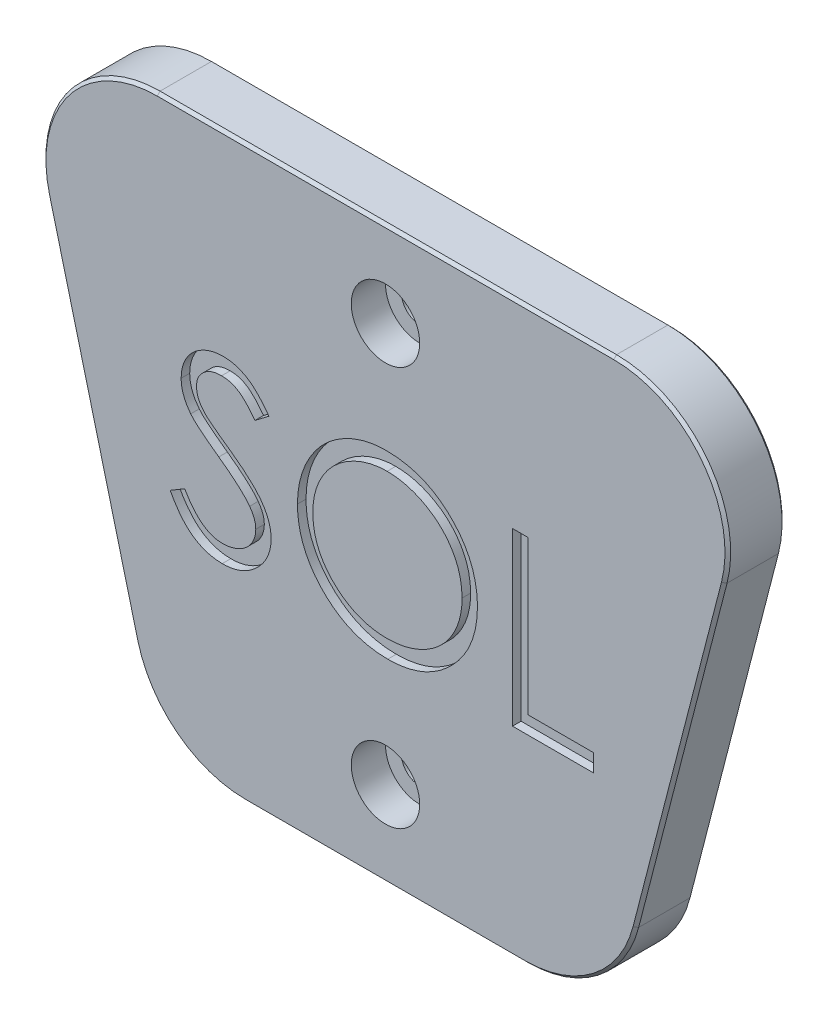
SolidWorks part; units mm, degrees
ref_plane "Front Plane" through (0, 0, 0) normal (0, 0, 1) x (1, 0, 0)
ref_plane "Top Plane" through (0, 0, 0) normal (0, 1, 0) x (1, 0, 0)
ref_plane "Right Plane" through (0, 0, 0) normal (1, 0, 0) x (0, 0, -1)
sketch "Sketch2" plane through (0, 0, 0) normal (0, 0, 1) x (1, 0, 0)
  line L0 (20, -80) -> (100, -80)
  line L6 (100, 20) -> (20, 20)
  line L8 (0.6351, -5) -> (20, -80)
  line L9 (119.3649, -5) -> (100, -80)
  line L10 (120, 23.0116) -> (120, 0)
  line L11 (0, 0) -> (0, 50.4461)
  line L12 (60, 20) -> (60, -80) construction
  arc A4 (119.3649, -5) -> (100, 20) centre (100, 0) ccw
  arc A5 (0.6351, -5) -> (20, 20) centre (20, 0) cw
  point P2 (120, 23.0116)
  point P7 (15.5222, -80)
  point P12 (120, 23.0116)
  point P15 (0, 0)
  point P21 (0, 0)
  dimension "D3" = 20
  dimension "D1" = 120
  dimension "D2" = 100
  dimension "D4" = 80
extrude "Boss-Extrude1" add sketch "Sketch2" along normal blind 10 contours A5 L8 L0 L9 A4 L6 | L12 L6 A5 L8 L0 region at (33.9449, -27.1175, 0) region at (86.0551, -27.1175, 0)
fillet "Fillet2" radius 20 2 edges at (20, -80, 5) (100, -80, 5)
sketch "Sketch10" plane through (0, 0, 10) normal (0, 0, 1) x (1, 0, 0)
  line L0 (60, 20) -> (60, -10) construction
  line L3 (60, 20) -> (60, -10) construction
  line L4 (60, -50) -> (60, -80) construction
  line L5 (60, 20) -> (60, -10) construction
  line L6 (60, -50) -> (60, -80) construction
  line L7 (100, 20) -> (20, 20) construction
  line L8 (35.4919, -80) -> (84.5081, -80) construction
  circle A1 centre (60, -65) radius 6
  circle A2 centre (60, 5) radius 6
  dimension "D1" = 12
  dimension "D2" = 15
  dimension "D3" = 15
extrude "Cut-Extrude6" cut sketch "Sketch10" against normal blind 6
sketch "Sketch11" plane through (0, 0, 4) normal (0, 0, 1) x (1, 0, 0)
  circle A0 centre (60, 5) radius 3.2
  circle A2 centre (60, -65) radius 3.2
  dimension "D1" = 6.4
extrude "Cut-Extrude7" cut sketch "Sketch11" against normal through all
sketch "Sketch13" plane through (0, 0, 10) normal (0, 0, 1) x (1, 0, 0)
  line L0 (35.4919, -80) -> (84.5081, -80) construction
  text T0 "SOL" font "Century Gothic" height 30
  dimension "D1" = 35
  dimension "D2" = 21.5
extrude "Cut-Extrude8" cut sketch "Sketch13" against normal blind 1.5
chamfer "Chamfer1" distance 0.5 angle 45 18 edges at (115.8114, 12.2474, 0) (4.1886, 12.2474, 0) (8.381, -35, 0) (111.619, -35, 0) (63.2, -65, 0) (63.2, 5, 0) (4.1886, 12.2474, 10) (115.8114, 12.2474, 10) (111.619, -35, 10) (8.381, -35, 10) (60, -80, 0) (60, 20, 0) (60, 20, 10) (96.7555, -75.8114, 0) (23.2445, -75.8114, 0) (60, -80, 10) (23.2445, -75.8114, 10) (96.7555, -75.8114, 10)
